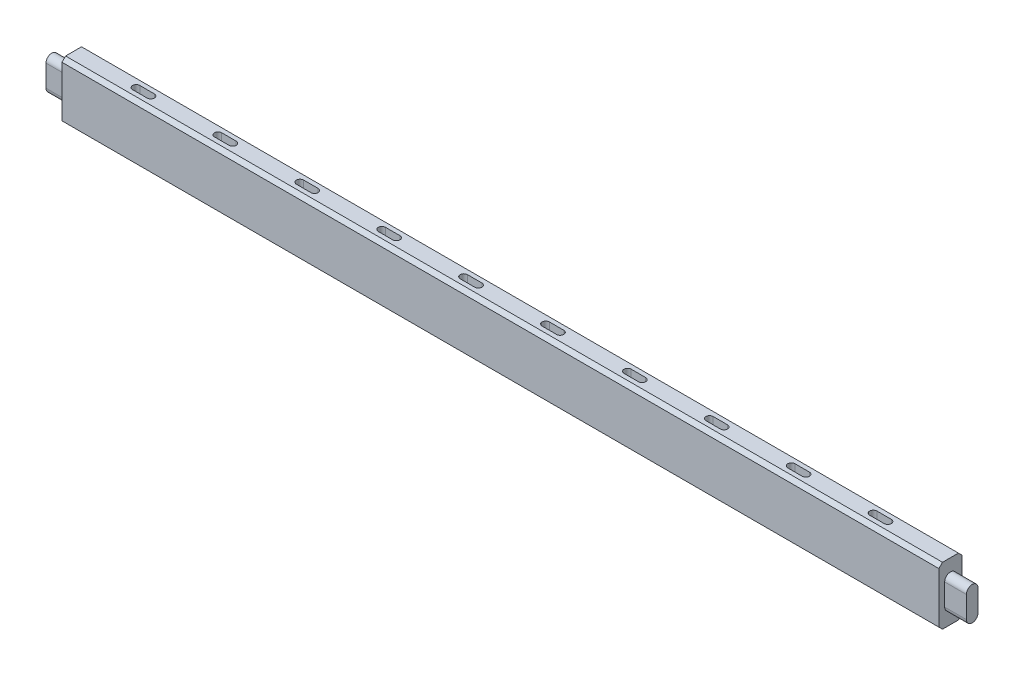
SolidWorks part; units mm, degrees
ref_plane "Front" through (0, 0, 0) normal (0, 0, 1) x (1, 0, 0)
ref_plane "Top" through (0, 0, 0) normal (0, 1, 0) x (1, 0, 0)
ref_plane "Right" through (0, 0, 0) normal (1, 0, 0) x (0, 0, -1)
sketch "Esquisse1" plane through (0, 0, 0) normal (0, 0, 1) x (1, 0, 0)
  line L1 (0, 0) -> (1210, 0)
  line L2 (0, 0) -> (0, 80)
  line L3 (0, 80) -> (1210, 80)
  line L4 (1210, 0) -> (1210, 80)
  dimension "D1" = 1210
  dimension "D2" = 80
extrude "Boss.-Extru.1" add sketch "Esquisse1" along normal blind 32
sketch "Esquisse2" plane through (0, 0, 0) normal (-1, 0, 0) x (0, 0, 1)
  line L0 (16, 0) -> (16, 80) construction
  line L1 (32, 0) -> (0, 0) construction
  line L2 (32, 80) -> (0, 80) construction
  line L3 (16, 25) -> (16, 55) construction
  line L4 (8, 25) -> (8, 55)
  line L5 (24, 25) -> (24, 55)
  arc A0 (8, 25) -> (24, 25) centre (16, 25) ccw
  arc A1 (24, 55) -> (8, 55) centre (16, 55) ccw
  point P8 (16, 40)
  dimension "D1" = 16
  dimension "D2" = 30
extrude "Boss.-Extru.2" add sketch "Esquisse2" along normal blind 30
extrude "Boss.-Extru.3" add sketch "Esquisse2<2>" against normal blind 30 from vertex starting at point (1210, 80, 0)
sketch "Esquisse2<2>" plane through (0, 0, 0) normal (-1, 0, 0) x (0, 0, 1) same geometry as "Esquisse2"
chamfer "Chanfrein1" distance 5 angle 45 4 edges at (605, 0, 32) (605, 0, 0) (605, 80, 0) (605, 80, 32)
sketch "Esquisse3" plane through (0, 80, 0) normal (0, 1, 0) x (1, 0, 0)
  line L0 (605, -27) -> (605, -5) construction
  line L5 (0, -27) -> (1210, -27) construction
  line L6 (1210, -5) -> (0, -5) construction
  line L7 (605, -16) -> (548.5, -16) construction
  line L8 (538.5, -16) -> (558.5, -16) construction
  line L9 (538.5, -11) -> (558.5, -11)
  line L10 (538.5, -21) -> (558.5, -21)
  line L11 (425.5, -16) -> (445.5, -16) construction
  line L12 (425.5, -11) -> (445.5, -11)
  line L13 (425.5, -21) -> (445.5, -21)
  line L14 (312.5, -16) -> (332.5, -16) construction
  line L15 (312.5, -11) -> (332.5, -11)
  line L16 (312.5, -21) -> (332.5, -21)
  line L17 (199.5, -16) -> (219.5, -16) construction
  line L18 (199.5, -11) -> (219.5, -11)
  line L19 (199.5, -21) -> (219.5, -21)
  line L20 (86.5, -16) -> (106.5, -16) construction
  line L21 (86.5, -11) -> (106.5, -11)
  line L22 (86.5, -21) -> (106.5, -21)
  line L29 (1123.5, -16) -> (1103.5, -16) construction
  line L30 (1123.5, -11) -> (1103.5, -11)
  line L31 (1123.5, -21) -> (1103.5, -21)
  line L32 (1010.5, -16) -> (990.5, -16) construction
  line L33 (1010.5, -11) -> (990.5, -11)
  line L34 (1010.5, -21) -> (990.5, -21)
  line L35 (897.5, -16) -> (877.5, -16) construction
  line L36 (897.5, -11) -> (877.5, -11)
  line L37 (897.5, -21) -> (877.5, -21)
  line L38 (784.5, -16) -> (764.5, -16) construction
  line L39 (784.5, -11) -> (764.5, -11)
  line L40 (784.5, -21) -> (764.5, -21)
  line L41 (671.5, -16) -> (651.5, -16) construction
  line L42 (671.5, -11) -> (651.5, -11)
  line L43 (671.5, -21) -> (651.5, -21)
  line L65 (-26, -16) -> (-6, -16) construction
  line L66 (-26, -11) -> (-6, -11)
  line L67 (-26, -21) -> (-6, -21)
  line L68 (-26.5, -16) -> (-6.5, -16) construction
  line L69 (-26.5, -11) -> (-6.5, -11)
  line L70 (-26.5, -21) -> (-6.5, -21)
  arc A0 (538.5, -11) -> (538.5, -21) centre (538.5, -16) ccw
  arc A1 (558.5, -21) -> (558.5, -11) centre (558.5, -16) ccw
  arc A2 (425.5, -11) -> (425.5, -21) centre (425.5, -16) ccw
  arc A3 (445.5, -21) -> (445.5, -11) centre (445.5, -16) ccw
  arc A4 (312.5, -11) -> (312.5, -21) centre (312.5, -16) ccw
  arc A5 (332.5, -21) -> (332.5, -11) centre (332.5, -16) ccw
  arc A6 (199.5, -11) -> (199.5, -21) centre (199.5, -16) ccw
  arc A7 (219.5, -21) -> (219.5, -11) centre (219.5, -16) ccw
  arc A8 (86.5, -11) -> (86.5, -21) centre (86.5, -16) ccw
  arc A9 (106.5, -21) -> (106.5, -11) centre (106.5, -16) ccw
  arc A14 (1123.5, -11) -> (1123.5, -21) centre (1123.5, -16) cw
  arc A15 (1103.5, -21) -> (1103.5, -11) centre (1103.5, -16) cw
  arc A16 (1010.5, -11) -> (1010.5, -21) centre (1010.5, -16) cw
  arc A17 (990.5, -21) -> (990.5, -11) centre (990.5, -16) cw
  arc A18 (897.5, -11) -> (897.5, -21) centre (897.5, -16) cw
  arc A19 (877.5, -21) -> (877.5, -11) centre (877.5, -16) cw
  arc A20 (784.5, -11) -> (784.5, -21) centre (784.5, -16) cw
  arc A21 (764.5, -21) -> (764.5, -11) centre (764.5, -16) cw
  arc A22 (671.5, -11) -> (671.5, -21) centre (671.5, -16) cw
  arc A23 (651.5, -21) -> (651.5, -11) centre (651.5, -16) cw
  arc A40 (-26.5, -11) -> (-26.5, -21) centre (-26.5, -16) ccw
  arc A41 (-6.5, -21) -> (-6.5, -11) centre (-6.5, -16) ccw
  point P10 (548.5, -16)
  point P19 (435.5, -16)
  point P26 (322.5, -16)
  point P33 (209.5, -16)
  point P40 (96.5, -16)
  point P59 (1113.5, -16)
  point P66 (1000.5, -16)
  point P73 (887.5, -16)
  point P80 (774.5, -16)
  point P87 (661.5, -16)
  point P94 (-11, -16)
  point P104 (-11, -16)
  point P111 (-11, -16)
  point P118 (-11, -16)
  point P125 (-16, -16)
  point P132 (-16, -16)
  point P139 (-16, -16)
  point P146 (-16, -16)
  point P153 (-16.5, -16)
  dimension "D1" = 10
  dimension "D2" = 113
  dimension "D3" = 20
  dimension "D4" = 6
  dimension "D5" = 113
extrude "Enlèv. mat.-Extru.1" cut sketch "Esquisse3" against normal blind 15
